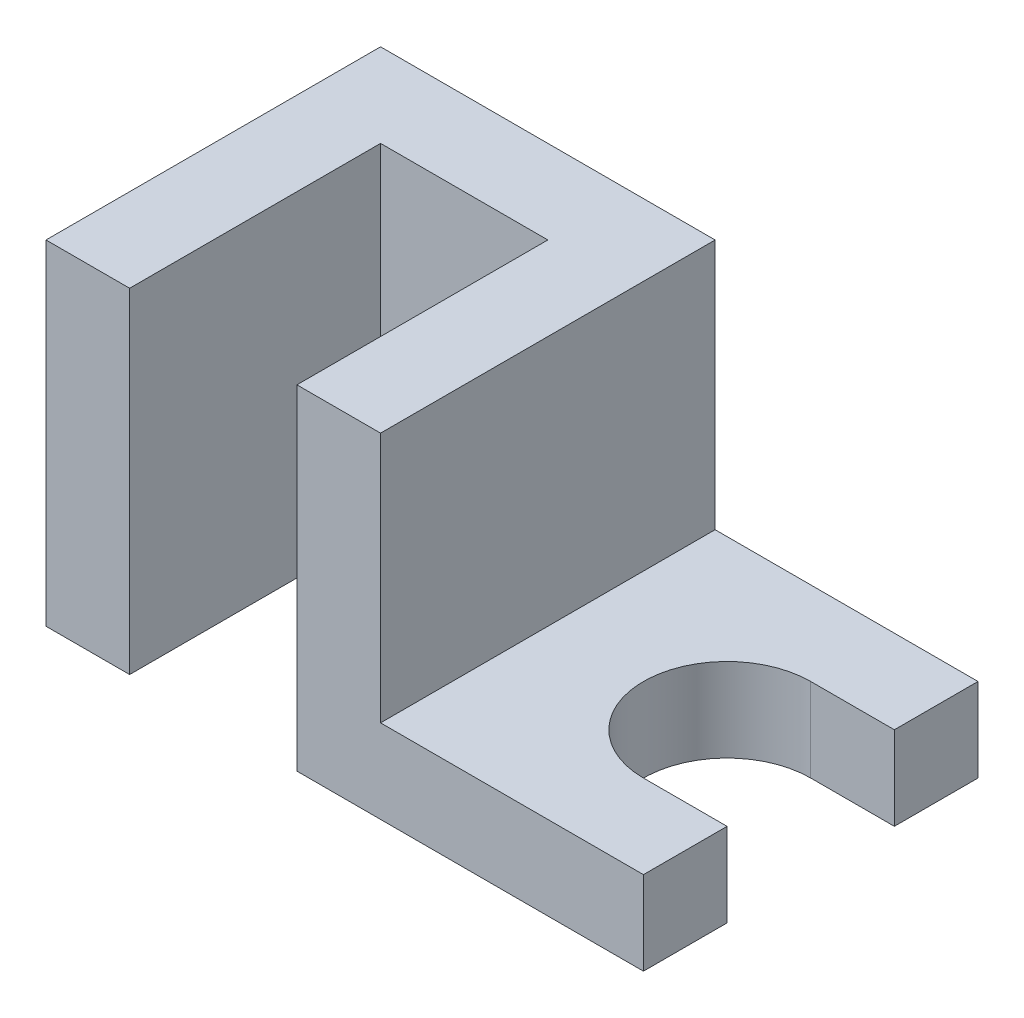
SolidWorks part; units mm, degrees
ref_plane "Front Plane" through (0, 0, 0) normal (0, 0, 1) x (1, 0, 0)
ref_plane "Top Plane" through (0, 0, 0) normal (0, 1, 0) x (1, 0, 0)
ref_plane "Right Plane" through (0, 0, 0) normal (1, 0, 0) x (0, 0, -1)
sketch "Sketch1" plane through (0, 0, 0) normal (0, 1, 0) x (1, 0, 0)
  line L0 (0, 0) -> (0, 28)
  line L1 (0, 28) -> (50, 28)
  line L2 (50, 28) -> (50, 21)
  line L3 (50, 21) -> (43, 21)
  line L4 (43, 7) -> (50, 7)
  line L5 (50, 7) -> (50, 0)
  line L6 (50, 0) -> (21, 0)
  line L7 (21, 0) -> (21, 21)
  line L8 (21, 21) -> (7, 21)
  line L9 (7, 21) -> (7, 0)
  line L10 (7, 0) -> (0, 0)
  line L11 (28, 28) -> (28, 0)
  arc A0 (43, 21) -> (43, 7) centre (43, 14) ccw
  dimension "D9" = 7
  dimension "D1" = 28
  dimension "D2" = 50
  dimension "D3" = 21
  dimension "D4" = 14
  dimension "D5" = 7
  dimension "D6" = 7
  dimension "D7" = 7
  dimension "D8" = 7
extrude "Boss-Extrude1" add sketch "Sketch1" along normal blind 7 contours A0 L3 L2 L1 L11 L6 L5 L4 region at (39, 0, -27.6439)
extrude "Boss-Extrude2" add sketch "Sketch1<3>" along normal blind 28 contours L11 L1 L0 L10 L9 L8 L7 L6 region at (0.396, 0, -14)
sketch "Sketch1<3>" plane through (0, 0, 0) normal (0, 1, 0) x (1, 0, 0) same geometry as "Sketch1"
